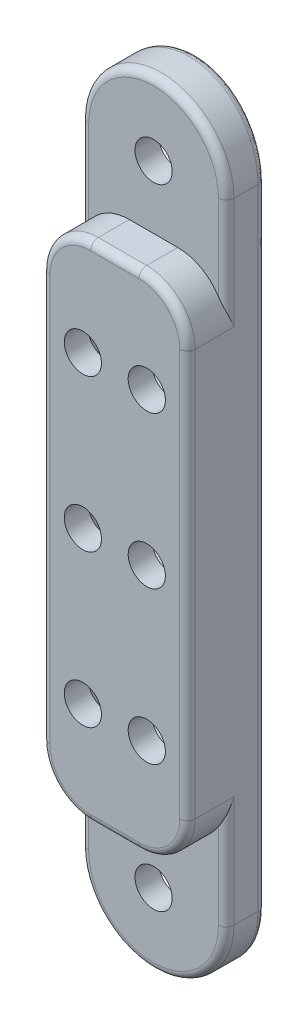
SolidWorks part; units mm, degrees
ref_plane "Front Plane" through (0, 0, 0) normal (0, 0, 1) x (1, 0, 0)
ref_plane "Top Plane" through (0, 0, 0) normal (0, 1, 0) x (1, 0, 0)
ref_plane "Right Plane" through (0, 0, 0) normal (1, 0, 0) x (0, 0, -1)
sketch "Sketch1" plane through (0, 0, 0) normal (0, 1, 0) x (1, 0, 0)
  line L1 (-4.1913, 1.27) -> (5.3337, 1.27)
  line L2 (-4.1913, 1.27) -> (-4.1913, 6.35)
  line L4 (5.3337, 1.27) -> (5.3337, 6.35)
  arc A0 (-4.1913, 6.35) -> (5.3337, 6.35) centre (0.5712, -31.4512) cw
  dimension "D3" = 38.1
  dimension "D1" = 9.525
  dimension "D2" = 5.08
extrude "Main profile" add sketch "Sketch1" along normal blind 50.8
sketch "Sketch2" plane through (0, 0, -1.27) normal (0, 0, 1) x (1, 0, 0)
  line L0 (-4.1913, 50.8) -> (-4.1913, 0) construction
  line L1 (5.3337, 50.8) -> (5.3337, 0) construction
  line L2 (-4.1913, 50.8) -> (5.3337, 50.8) construction
  line L3 (-4.1913, 0) -> (5.3337, 0) construction
  line L4 (-4.1913, 46.0375) -> (-4.1913, 4.7625)
  line L5 (5.3337, 46.0375) -> (5.3337, 4.7625)
  line L10 (-4.1913, 0) -> (5.3337, 0)
  line L11 (5.3337, 0) -> (5.3337, 50.8)
  line L12 (5.3337, 50.8) -> (-4.1913, 50.8)
  line L13 (-4.1913, 50.8) -> (-4.1913, 0)
  line L14 (-4.1913, 0) -> (5.3337, 0)
  line L15 (5.3337, 0) -> (5.3337, 50.8)
  line L16 (5.3337, 50.8) -> (-4.1913, 50.8)
  line L17 (-4.1913, 50.8) -> (-4.1913, 0)
  arc A0 (-4.1913, 46.0375) -> (5.3337, 46.0375) centre (0.5712, 46.0375) cw
  arc A1 (5.3337, 4.7625) -> (-4.1913, 4.7625) centre (0.5712, 4.7625) cw
  line M9 (-4.1913, 0) -> (5.3337, 0)
  line M10 (5.3337, 0) -> (5.3337, 50.8)
  line M11 (5.3337, 50.8) -> (-4.1913, 50.8)
  line M12 (-4.1913, 50.8) -> (-4.1913, 0)
  dimension "D2" = 4.7625
  dimension "D1" = 0
extrude "End rounds" cut sketch "Sketch2" against normal blind 25.4 contours A0 L16 M12 | A0 M11 M10 | A1 L14 M10 | A1 M9 M12 region at (-3.1275, 49.7362, -1.27) region at (-3.1275, 1.0638, -1.27) region at (4.2699, 49.7362, -1.27) region at (4.2699, 1.0638, -1.27)
sketch "Sketch3" plane through (-4.1913, 0, 0) normal (-1, 0, 0) x (0, 0, 1)
  line L1 (-1.27, 46.0375) -> (-1.27, 50.8) construction
  line L4 (-1.27, 4.7625) -> (-1.27, 46.0375)
  line L7 (-1.27, 46.0375) -> (-6.35, 46.0375)
  line L8 (-1.27, 4.7625) -> (-1.27, 46.0375)
  line L12 (-1.27, 0) -> (-1.27, 4.7625) construction
  line L14 (-3.81, 25.4) -> (-1.27, 25.4) construction
  line L15 (-1.27, 46.0375) -> (-1.27, 50.8)
  line L17 (-3.81, 41.91) -> (-1.27, 41.91)
  line L18 (-1.27, 0) -> (-1.27, 4.7625)
  line L19 (-1.27, 8.89) -> (-3.81, 8.89)
  line L20 (-2.54, 8.89) -> (-2.54, 41.91) construction
  line L21 (-1.27, 50.8) -> (-3.81, 50.8)
  line L22 (-1.27, 50.8) -> (-1.27, 0)
  line L23 (-1.27, 0) -> (-3.81, 0)
  line L24 (-3.81, 50.8) -> (-3.81, 0)
  line L29 (-6.35, 4.7625) -> (-1.27, 4.7625)
  line L31 (-6.35, 46.0375) -> (-6.35, 4.7625)
  line L32 (-6.35, 46.0375) -> (-6.35, 4.7625)
  spline S0 degree 2 poles (-6.6488, 50.8) (-6.35, 48.4094) (-6.35, 46.0375) knots 0 0 0 0.468627 0.468627 0.468627 weights 0.033338 0.035569 0.037801 construction
  spline S1 degree 2 poles (-6.35, 4.7625) (-6.35, 2.3906) (-6.6488, 0) knots 0.468627 0.468627 0.468627 1 1 1 weights 0.037801 0.040332 0.042863 construction
  spline S2 degree 2 poles (-6.6488, 50.8) (-6.35, 48.4094) (-6.35, 46.0375) knots 0 0 0 0.468627 0.468627 0.468627 weights 0.033338 0.035569 0.037801
  spline S3 degree 2 poles (-6.35, 4.7625) (-6.35, 2.3906) (-6.6488, 0) knots 0.468627 0.468627 0.468627 1 1 1 weights 0.037801 0.040332 0.042863
  point P19 (-2.54, 25.4)
  line M11 (-1.27, 4.7625) -> (-1.27, 46.0375)
  line M12 (-1.27, 46.0375) -> (-6.35, 46.0375)
  line M14 (-6.35, 4.7625) -> (-1.27, 4.7625)
  dimension "D2" = 2.54
  dimension "D3" = 8.89
  dimension "D1" = 0
extrude "Locating Flange" cut sketch "Sketch3" against normal through all contours L24 L23 L18 M14 | L19 L24 M14 M11 | L24 L17 L8 M12 | L21 L24 L15 M12 region at (-4.1913, 6.8262, -2.54) region at (-4.1913, 2.3813, -2.54) region at (-4.1913, 43.9737, -2.54) region at (-4.1913, 48.4188, -2.54)
ref_plane "Top Surface" through (0, 0, -6.6488) normal (0, 0, -1) x (-1, 0, 0)
sketch "Sketch4" plane through (0, 0, -6.6488) normal (0, 0, -1) x (-1, 0, 0)
  line L0 (-0.5712, 18.796) -> (-0.5712, 32.004) construction
  line L1 (-2.3492, 38.735) -> (1.2068, 38.735)
  line L2 (-5.3337, 46.0375) -> (-5.3337, 4.7625)
  line L6 (-3.9367, 37.1475) -> (-3.9367, 33.5915)
  line L7 (-2.3492, 32.004) -> (1.2068, 32.004)
  line L8 (2.7943, 37.1475) -> (2.7943, 33.5915)
  line L9 (-2.3492, 28.7655) -> (1.2068, 28.7655)
  line L14 (-3.9367, 27.178) -> (-3.9367, 23.622)
  line L16 (-2.3492, 22.0345) -> (1.2068, 22.0345)
  line L18 (4.1913, 8.89) -> (4.1913, 41.91)
  line L19 (-5.3337, 8.89) -> (4.1913, 8.89)
  line L20 (-5.3337, 41.91) -> (-5.3337, 8.89)
  line L21 (4.1913, 41.91) -> (-5.3337, 41.91)
  line L22 (4.1913, 8.89) -> (4.1913, 41.91)
  line L23 (-5.3337, 8.89) -> (4.1913, 8.89)
  line L24 (-5.3337, 41.91) -> (-5.3337, 8.89)
  line L25 (4.1913, 41.91) -> (-5.3337, 41.91)
  line L26 (2.7943, 27.178) -> (2.7943, 23.622)
  line L27 (-2.3492, 18.796) -> (1.2068, 18.796)
  line L28 (-3.9367, 17.2085) -> (-3.9367, 13.6525)
  line L29 (-2.3492, 12.065) -> (1.2068, 12.065)
  line L30 (2.7943, 17.2085) -> (2.7943, 13.6525)
  line L31 (-5.3337, 25.4) -> (4.1913, 25.4) construction
  line L34 (-5.3337, 46.0375) -> (-5.3337, 4.7625)
  line L36 (4.1913, 4.7625) -> (4.1913, 46.0375)
  line L37 (4.1913, 4.7625) -> (4.1913, 46.0375)
  arc A0 (1.2068, 12.065) -> (2.7943, 13.6525) centre (1.2068, 13.6525) ccw
  arc A1 (-3.9367, 13.6525) -> (-2.3492, 12.065) centre (-2.3492, 13.6525) ccw
  arc A2 (4.1913, 46.0375) -> (-5.3337, 46.0375) centre (-0.5712, 46.0375) ccw
  arc A3 (4.1913, 46.0375) -> (-5.3337, 46.0375) centre (-0.5712, 46.0375) ccw
  arc A6 (-5.3337, 4.7625) -> (4.1913, 4.7625) centre (-0.5712, 4.7625) ccw
  arc A7 (-5.3337, 4.7625) -> (4.1913, 4.7625) centre (-0.5712, 4.7625) ccw
  arc A8 (1.2068, 18.796) -> (2.7943, 17.2085) centre (1.2068, 17.2085) cw
  arc A9 (-2.3492, 18.796) -> (-3.9367, 17.2085) centre (-2.3492, 17.2085) ccw
  arc A10 (1.2068, 38.735) -> (2.7943, 37.1475) centre (1.2068, 37.1475) cw
  arc A11 (1.2068, 32.004) -> (2.7943, 33.5915) centre (1.2068, 33.5915) ccw
  arc A12 (-3.9367, 33.5915) -> (-2.3492, 32.004) centre (-2.3492, 33.5915) ccw
  arc A13 (1.2068, 22.0345) -> (2.7943, 23.622) centre (1.2068, 23.622) ccw
  arc A14 (-2.3492, 28.7655) -> (-3.9367, 27.178) centre (-2.3492, 27.178) ccw
  arc A15 (-3.9367, 23.622) -> (-2.3492, 22.0345) centre (-2.3492, 23.622) ccw
  arc A16 (1.2068, 28.7655) -> (2.7943, 27.178) centre (1.2068, 27.178) cw
  arc A17 (-2.3492, 38.735) -> (-3.9367, 37.1475) centre (-2.3492, 37.1475) ccw
  point P23 (-0.5712, 18.796)
  point P27 (-0.5712, 25.4)
  point P28 (-0.5712, 28.7655)
  point P57 (-0.5712, 25.4)
  dimension "D6" = 1.5875
  dimension "D4" = 3.175
  dimension "D5" = 3.175
  dimension "D7" = 6.731
  dimension "D1" = 0
  dimension "D3" = 0
extrude "Button Pockets" cut sketch "Sketch4" against normal blind 3.81 contours L16 L0 L9 L14 | L0 L16 L26 L9 | L30 L27 L28 L29 | L6 A12 L7 A11 L8 A10 L1 A17 region at (0.5712, 25.4, -6.6488) region at (0.5712, 15.4305, -6.6488)
sketch "Hole Locations" plane through (0, 0, -6.6488) normal (0, 0, -1) x (-1, 0, 0)
  line L2 (-5.3337, 46.0375) -> (-5.3337, 4.7625)
  line L6 (-5.3337, 46.0375) -> (-5.3337, 4.7625)
  line L8 (4.1913, 4.7625) -> (4.1913, 46.0375)
  line L9 (4.1913, 4.7625) -> (4.1913, 46.0375)
  arc A2 (4.1913, 46.0375) -> (-5.3337, 46.0375) centre (-0.5712, 46.0375) ccw
  arc A3 (-5.3337, 4.7625) -> (4.1913, 4.7625) centre (-0.5712, 4.7625) ccw
  arc A4 (4.1913, 46.0375) -> (-5.3337, 46.0375) centre (-0.5712, 46.0375) ccw
  arc A5 (-5.3337, 4.7625) -> (4.1913, 4.7625) centre (-0.5712, 4.7625) ccw
  point P5 (-0.5712, 46.0375)
  point P8 (-0.5712, 4.7625)
  dimension "D1" = 0
hole_wizard "CBORE for #2 Binding Head Machine Screw1" positions "Sketch7" profile "Sketch9" counterbore size "#2" standard "ANSI Inch" end condition through all
sketch "Sketch7" plane through (0, 0, -6.6488) normal (0, 0, -1) x (-1, 0, 0)
  point P0 (-0.5712, 46.0375)
  point P3 (-0.5712, 4.7625)
sketch "Sketch9" plane through (0.5712, 46.0375, -6.6488) normal (1, 0, 0) x (0, 1, 0)
  line L0 (0, 0) -> (0, 5.3788)
  line L1 (0, 5.3788) -> (1.2192, 5.3788)
  line L3 (1.2192, 5.3788) -> (1.2192, 1.27)
  line L4 (1.2192, 1.27) -> (2.7788, 1.27)
  line L5 (2.7788, 1.27) -> (2.7788, 0)
  line L7 (2.7788, 0) -> (0, 0)
  line L11 (0, -6.35) -> (0, 107.95) construction
  dimension "Thru Hole Dia." = 2.4384
  dimension "Thru Hole Depth" = 5.3788
  dimension "C'Bore Dia." = 5.5575
  dimension "C'Bore Depth" = 1.27
sketch "Sketch13" plane through (0, 0, -1.27) normal (0, 0, 1) x (1, 0, 0)
  line L0 (-1.2068, 18.796) -> (2.3492, 18.796) construction
  line L1 (3.9367, 17.2085) -> (3.9367, 13.6525) construction
  line L2 (2.3492, 12.065) -> (-1.2068, 12.065) construction
  line L3 (-2.7943, 13.6525) -> (-2.7943, 17.2085) construction
  line L4 (-1.2068, 28.7655) -> (2.3492, 28.7655) construction
  line L5 (3.9367, 27.178) -> (3.9367, 23.622) construction
  line L6 (2.3492, 22.0345) -> (-1.2068, 22.0345) construction
  line L7 (-2.7943, 23.622) -> (-2.7943, 27.178) construction
  line L8 (3.9367, 37.1475) -> (3.9367, 33.5915) construction
  line L9 (2.3492, 32.004) -> (-1.2068, 32.004) construction
  line L10 (-2.7943, 33.5915) -> (-2.7943, 37.1475) construction
  line L11 (-1.2068, 38.735) -> (2.3492, 38.735) construction
  line L12 (-4.1913, 41.91) -> (-4.1913, 8.89) construction
  line L13 (-4.1913, 8.89) -> (5.3337, 8.89) construction
  line L14 (5.3337, 8.89) -> (5.3337, 41.91) construction
  line L15 (5.3337, 41.91) -> (-4.1913, 41.91) construction
  line L16 (-1.2068, 18.796) -> (2.3492, 18.796)
  line L17 (3.9367, 17.2085) -> (3.9367, 13.6525)
  line L18 (2.3492, 12.065) -> (-1.2068, 12.065)
  line L19 (-2.7943, 13.6525) -> (-2.7943, 17.2085)
  line L20 (-1.2068, 28.7655) -> (2.3492, 28.7655)
  line L21 (3.9367, 27.178) -> (3.9367, 23.622)
  line L22 (2.3492, 22.0345) -> (-1.2068, 22.0345)
  line L23 (-2.7943, 23.622) -> (-2.7943, 27.178)
  line L24 (3.9367, 37.1475) -> (3.9367, 33.5915)
  line L25 (2.3492, 32.004) -> (-1.2068, 32.004)
  line L26 (-2.7943, 33.5915) -> (-2.7943, 37.1475)
  line L27 (-1.2068, 38.735) -> (2.3492, 38.735)
  line L28 (-4.1913, 41.91) -> (-4.1913, 8.89)
  line L29 (-4.1913, 8.89) -> (5.3337, 8.89)
  line L30 (5.3337, 8.89) -> (5.3337, 41.91)
  line L31 (5.3337, 41.91) -> (-4.1913, 41.91)
  line L32 (-1.5243, 35.3695) -> (2.6667, 35.3695) construction
  arc A0 (3.9367, 17.2085) -> (2.3492, 18.796) centre (2.3492, 17.2085) ccw construction
  arc A1 (2.3492, 12.065) -> (3.9367, 13.6525) centre (2.3492, 13.6525) ccw construction
  arc A2 (-2.7943, 13.6525) -> (-1.2068, 12.065) centre (-1.2068, 13.6525) ccw construction
  arc A3 (-1.2068, 18.796) -> (-2.7943, 17.2085) centre (-1.2068, 17.2085) ccw construction
  arc A4 (-1.2068, 28.7655) -> (-2.7943, 27.178) centre (-1.2068, 27.178) ccw construction
  arc A5 (3.9367, 27.178) -> (2.3492, 28.7655) centre (2.3492, 27.178) ccw construction
  arc A6 (2.3492, 22.0345) -> (3.9367, 23.622) centre (2.3492, 23.622) ccw construction
  arc A7 (-2.7943, 23.622) -> (-1.2068, 22.0345) centre (-1.2068, 23.622) ccw construction
  arc A8 (3.9367, 37.1475) -> (2.3492, 38.735) centre (2.3492, 37.1475) ccw construction
  arc A9 (2.3492, 32.004) -> (3.9367, 33.5915) centre (2.3492, 33.5915) ccw construction
  arc A10 (-2.7943, 33.5915) -> (-1.2068, 32.004) centre (-1.2068, 33.5915) ccw construction
  arc A11 (-1.2068, 38.735) -> (-2.7943, 37.1475) centre (-1.2068, 37.1475) ccw construction
  arc A12 (3.9367, 17.2085) -> (2.3492, 18.796) centre (2.3492, 17.2085) ccw
  arc A13 (2.3492, 12.065) -> (3.9367, 13.6525) centre (2.3492, 13.6525) ccw
  arc A14 (-2.7943, 13.6525) -> (-1.2068, 12.065) centre (-1.2068, 13.6525) ccw
  arc A15 (-1.2068, 18.796) -> (-2.7943, 17.2085) centre (-1.2068, 17.2085) ccw
  arc A16 (-1.2068, 28.7655) -> (-2.7943, 27.178) centre (-1.2068, 27.178) ccw
  arc A17 (3.9367, 27.178) -> (2.3492, 28.7655) centre (2.3492, 27.178) ccw
  arc A18 (2.3492, 22.0345) -> (3.9367, 23.622) centre (2.3492, 23.622) ccw
  arc A19 (-2.7943, 23.622) -> (-1.2068, 22.0345) centre (-1.2068, 23.622) ccw
  arc A20 (3.9367, 37.1475) -> (2.3492, 38.735) centre (2.3492, 37.1475) ccw
  arc A21 (2.3492, 32.004) -> (3.9367, 33.5915) centre (2.3492, 33.5915) ccw
  arc A22 (-2.7943, 33.5915) -> (-1.2068, 32.004) centre (-1.2068, 33.5915) ccw
  arc A23 (-1.2068, 38.735) -> (-2.7943, 37.1475) centre (-1.2068, 37.1475) ccw
  point P4 (-1.5243, 35.3695)
  point P5 (2.6667, 35.3695)
  point P9 (2.6667, 25.4)
  point P10 (2.6667, 15.4305)
  point P14 (-1.5243, 15.4305)
  point P15 (-1.5243, 25.4)
  point P18 (0.5712, 35.3695)
  point P19 (0.5712, 41.91)
  point P27 (3.9367, 25.4)
  point P37 (3.9367, 15.4305)
  point P39 (3.9367, 35.3695)
  dimension "D1" = 4.191
hole_wizard "#41 (0.096) Diameter Hole1" positions "Sketch14" profile "Sketch16" hole size "#41" standard "ANSI Inch" end condition through all
sketch "Sketch14" plane through (0, 0, -1.27) normal (0, 0, 1) x (1, 0, 0)
  point P0 (-1.5243, 35.3695)
  point P3 (2.6667, 35.3695)
  point P6 (2.6667, 25.4)
  point P9 (-1.5243, 25.4)
  point P12 (-1.5243, 15.4305)
  point P15 (2.6667, 15.4305)
sketch "Sketch16" plane through (-1.5243, 35.3695, -1.27) normal (1, 0, 0) x (0, -1, 0)
  line L0 (0, 0) -> (0, 5.3788)
  line L1 (0, 5.3788) -> (1.2192, 5.3788)
  line L2 (1.2192, 5.3788) -> (1.2192, 0)
  line L5 (1.2192, 0) -> (0, 0)
  line L11 (0, -6.35) -> (0, 107.95) construction
  dimension "Thru Hole Dia." = 2.4384
  dimension "Thru Hole Depth" = 5.3788
fillet "Fillet1" radius 0.508 16 edges at (-4.1913, 43.9737, -3.81) (0.5712, 50.8, -3.81) (0.5712, 50.8, -6.6488) (-4.1913, 25.4, -6.35) (0.5712, 0, -6.6488) (-4.1913, 6.8262, -3.81) (0.5712, 0, -3.81) (3.2774, 46.6683, -6.5526) (5.3337, 25.4, -1.27) (5.3337, 43.9737, -3.81) (5.3337, 25.4, -6.35) (5.3337, 6.8262, -3.81) (0.5712, 41.91, -1.27) (-4.1913, 25.4, -1.27) (0.5712, 8.89, -1.27) (3.2774, 5.3933, -6.5526)
fillet "Fillet2" radius 3.175 8 edges at (5.1849, 41.7612, -1.4188) (-4.0425, 41.7612, -1.4188) (-4.0425, 9.0388, -1.4188) (5.1849, 9.0388, -1.4188) (5.3337, 8.89, -3.048) (-4.1913, 8.89, -3.048) (-4.1913, 41.91, -3.048) (5.3337, 41.91, -3.048)
